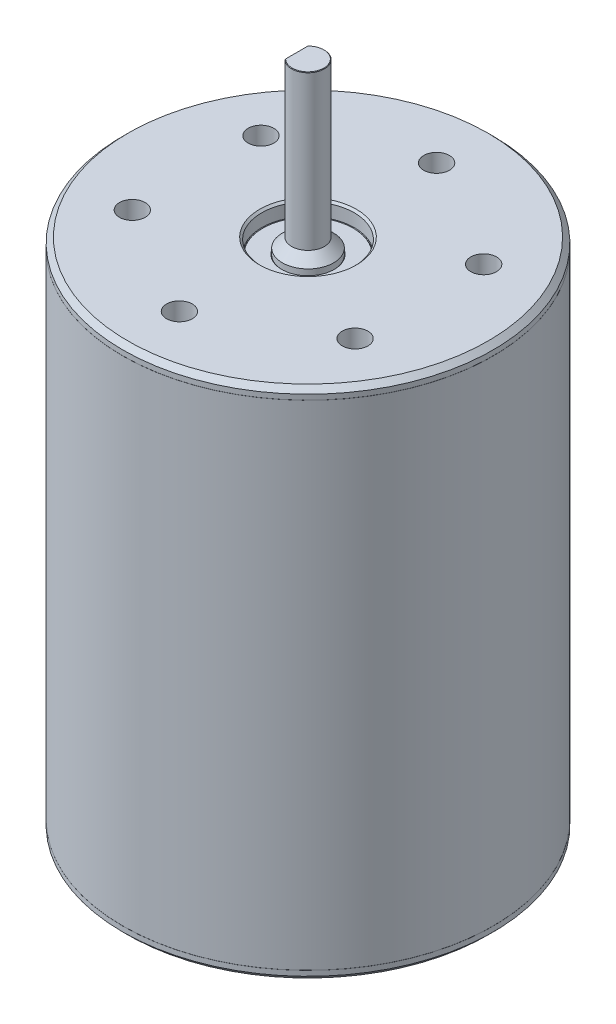
SolidWorks part; units mm, degrees
ref_plane "Plan de face" through (0, 0, 0) normal (0, 0, 1) x (1, 0, 0)
ref_plane "Plan de dessus" through (0, 0, 0) normal (0, 1, 0) x (1, 0, 0)
ref_plane "Plan de droite" through (0, 0, 0) normal (1, 0, 0) x (0, 0, -1)
sketch "Esquisse1" plane through (0, 0, 0) normal (0, 0, 1) x (1, 0, 0)
  line L0 (0, -4.9211) -> (0, 66.0276) construction
  line L1 (0, 65) -> (-1.5375, 65)
  line L2 (-1.5875, 64.95) -> (-1.5875, 50)
  line L3 (-1.5875, 50) -> (-2.5, 49.0875)
  line L4 (-2.5, 49.0875) -> (-2.5, 48.5)
  line L5 (-2.5, 48.5) -> (-2.55, 48.55)
  line L6 (-2.55, 48.55) -> (-4.4, 48.55)
  line L7 (-4.4, 48.55) -> (-4.45, 48.5)
  line L8 (-4.45, 48.5) -> (-4.5, 48.55)
  line L9 (-4.5, 48.55) -> (-4.5, 49.8)
  line L10 (-4.5, 49.8) -> (-4.7, 50)
  line L11 (-4.7, 50) -> (-17.5, 50)
  line L12 (-17.5, 50) -> (-18, 49.5)
  line L13 (-18, 49.5) -> (-18, 49)
  line L14 (-18, 49) -> (-17.995, 48.995)
  line L15 (-17.995, 48.995) -> (-18, 48.99)
  line L16 (-18, 48.99) -> (-18, 1.01)
  line L17 (-18, 1.01) -> (-17.995, 1.005)
  line L18 (-17.995, 1.005) -> (-18, 1)
  line L19 (-18, 1) -> (-18, 0.5)
  line L20 (-18, 0.5) -> (-17.5, 0)
  line L21 (-17.5, 0) -> (-4.7, 0)
  line L22 (-4.7, 0) -> (-4.5, 0.2)
  line L23 (-4.5, 0.2) -> (-4.5, 1.45)
  line L24 (-4.5, 1.45) -> (-4.45, 1.5)
  line L25 (-4.45, 1.5) -> (-4.4, 1.45)
  line L26 (-4.4, 1.45) -> (-2.55, 1.45)
  line L27 (-2.55, 1.45) -> (-2.5, 1.5)
  line L28 (-2.5, 1.5) -> (-2.45, 1.45)
  line L29 (-2.45, 1.45) -> (0, 1.45)
  line L30 (-1.5375, 65) -> (-1.5875, 64.95)
  line L31 (0, 65) -> (0, 1.45)
  dimension "D1" = 0.2
  dimension "D2" = 36
  dimension "D3" = 3.175
  dimension "D4" = 5
  dimension "D5" = 15
  dimension "D6" = 45
  dimension "D7" = 1.45
  dimension "D8" = 9
  dimension "D9" = 0.05
  dimension "D10" = 50
  dimension "D11" = 0.5
  dimension "D12" = 0.5
  dimension "D13" = 0.01
revolve "Révolution1" add sketch "Esquisse1" angle 360 about L0
sketch "Esquisse2" plane through (0, 65, 0) normal (0, 1, 0) x (1, 0, 0)
  line L1 (-1.5875, -1.1565) -> (-1.0875, -1.1565)
  line L2 (-1.5875, -1.1565) -> (-1.5875, 1.1565)
  line L3 (-1.5875, 1.1565) -> (-1.0875, 1.1565)
  line L4 (-1.0875, -1.1565) -> (-1.0875, 1.1565)
  line L5 (-1.5875, -1.1565) -> (-1.0875, 1.1565) construction
  line L6 (-1.5875, 1.1565) -> (-1.0875, -1.1565) construction
  circle A0 centre (0, 0) radius 1.5875 construction
  point P0 (-1.3375, 0)
  dimension "D1" = 0.5
extrude "Enlèv. mat.-Extru.1" cut sketch "Esquisse2" against normal offset from surface (12 mm away) 3 up to face at (0, 50, -17.5)
hole_wizard "Trou taraudé M31" positions "Esquisse5" profile "Esquisse4" tap size "M3" standard "ISO"
sketch "Esquisse5" plane through (0, 50, 0) normal (0, 1, 0) x (1, 0, 0)
  point P0 (0, 12.5)
  dimension "D1" = 12.5
sketch "Esquisse4" plane through (0, 50, -12.5) normal (1, 0, 0) x (0, 0, 1)
  line L0 (0, 0) -> (0, 7.7511)
  line L1 (0, 7.7511) -> (1.25, 7)
  line L2 (1.25, 7) -> (1.25, 0)
  line L5 (1.25, 0) -> (0, 0)
  line L10 (0, 7.7511) -> (-1.25, 7) construction
  line L11 (0, -6.35) -> (0, 107.95) construction
  dimension "Diamètre du trou pour taraudage" = 2.5
  dimension "Profondeur du trou pour taraudage" = 7
  dimension "Angle de pointe" = 118
cosmetic thread "Filetage de perçage1" parameters "D1"=6, "D2"=3
pattern_circular "Répétition circulaire1" count 6 over 360 about axis through (0, -4.9211, 0) along (0, -1, 0) of "Trou taraudé M31" reverse direction yes
ref_axis "Axe1" through (0, 91.7526, 0) along (0, -1, 0)
